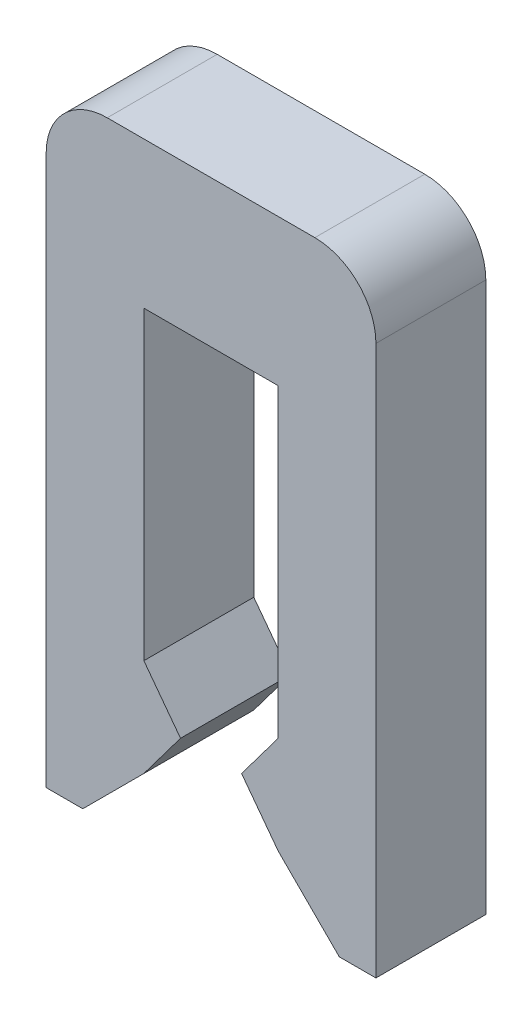
SolidWorks part; units mm, degrees
ref_plane "Спереди" through (0, 0, 0) normal (0, 0, 1) x (1, 0, 0)
ref_plane "Сверху" through (0, 0, 0) normal (0, 1, 0) x (1, 0, 0)
ref_plane "Справа" through (0, 0, 0) normal (1, 0, 0) x (0, 0, -1)
sketch "Эскиз1" plane through (0, 0, 0) normal (0, 0, 1) x (1, 0, 0)
  line L0 (-0.55, 0) -> (0.55, 0)
  line L1 (0.55, 0) -> (0.55, -3.8)
  line L2 (0.55, -3.8) -> (1.35, -3.8)
  line L3 (1.35, -3.8) -> (1.35, 1.2)
  line L4 (1.35, 1.2) -> (-1.35, 1.2)
  line L5 (0, 1.2) -> (0, 0) construction
  line L6 (-0.55, 0) -> (-0.55, -3.8)
  line L7 (-0.55, -3.8) -> (-1.35, -3.8)
  line L8 (-1.35, -3.8) -> (-1.35, 1.2)
  dimension "D1" = 0.55
  dimension "D2" = 0.8
  dimension "D4" = 3.8
  dimension "D5" = 5
extrude "Бобышка-Вытянуть1" add sketch "Эскиз1" along normal blind 0.9
chamfer "Фаска1" distance 0.5 angle 45 2 edges at (-0.55, -3.8, 0.45) (0.55, -3.8, 0.45)
fillet "Скругление1" radius 0.5 2 edges at (1.35, 1.2, 0.45) (-1.35, 1.2, 0.45)
sketch "Эскиз2" plane through (0, 0, 0.9) normal (0, 0, 1) x (1, 0, 0)
  line L0 (-0.55, -3.3) -> (-0.55, -2.5)
  line L1 (-0.55, -3.3) -> (-0.55, 0) construction
  line L2 (-0.55, -2.5) -> (-0.25, -2.9)
  line L3 (-0.25, -2.9) -> (-0.55, -3.3)
  line L4 (-0.25, -2.9) -> (-0.55, -2.9) construction
  dimension "D1" = 0.3
  dimension "D2" = 0.8
extrude "Бобышка-Вытянуть2" add sketch "Эскиз2" against normal blind 0.9
mirror "Зеркальное отражение1" about plane through (0, 0, 0) normal (1, 0, 0) of "Бобышка-Вытянуть2"
